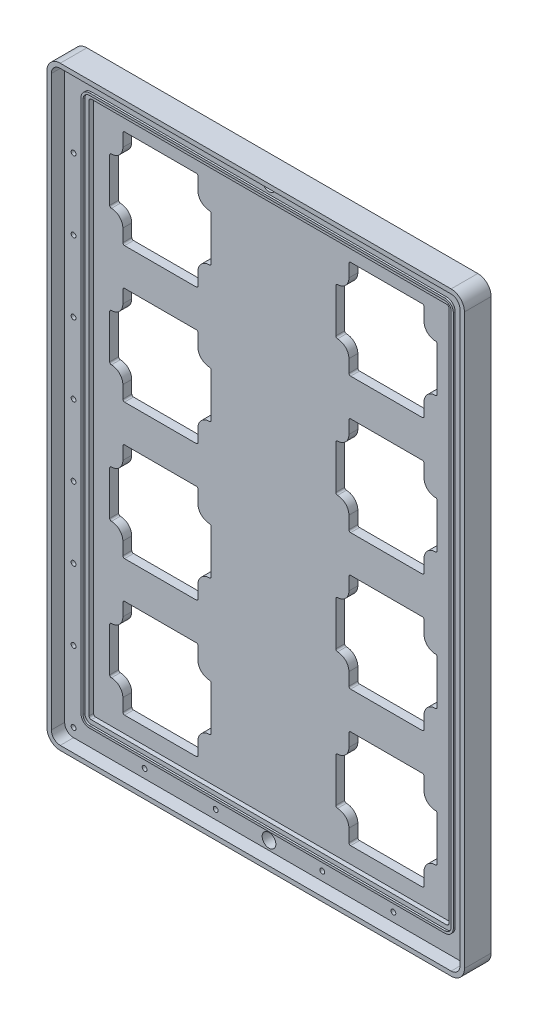
SolidWorks part; units mm, degrees
ref_plane "Front Plane" through (0, 0, 0) normal (0, 0, 1) x (1, 0, 0)
ref_plane "Top Plane" through (0, 0, 0) normal (0, 1, 0) x (1, 0, 0)
ref_plane "Right Plane" through (0, 0, 0) normal (1, 0, 0) x (0, 0, -1)
sketch "Sketch1" plane through (0, 0, 0) normal (0, 0, 1) x (1, 0, 0)
  line L1 (0, 0) -> (292.1, 0)
  line L2 (0, 0) -> (0, 419.1)
  line L3 (0, 419.1) -> (292.1, 419.1)
  line L4 (292.1, 0) -> (292.1, 419.1)
  dimension "D1" = 419.1
  dimension "D2" = 292.1
extrude "Boss-Extrude1" add sketch "Sketch1" along normal blind 9.525
sketch "Sketch4" plane through (0, 0, 9.525) normal (0, 0, 1) x (1, 0, 0)
  line L3 (0, 419.1) -> (0, 0) construction
  line L4 (6.35, 412.75) -> (285.75, 412.75) construction
  line L5 (6.35, 412.75) -> (6.35, 6.35) construction
  line L6 (6.35, 6.35) -> (285.75, 6.35) construction
  line L7 (285.75, 412.75) -> (285.75, 6.35) construction
  line L8 (292.1, 419.1) -> (0, 419.1) construction
  line L9 (292.1, 0) -> (292.1, 419.1) construction
  line L10 (0, 0) -> (292.1, 0) construction
  circle A0 centre (6.35, 6.35) radius 1.7272
  circle A1 centre (6.35, 412.75) radius 1.7272
  circle A2 centre (285.75, 412.75) radius 1.7272
  circle A3 centre (285.75, 6.35) radius 1.7272
  dimension "D5" = 3.4544
  dimension "D1" = 6.35
  dimension "D2" = 6.35
  dimension "D3" = 6.35
  dimension "D4" = 6.35
extrude "Cut-Extrude1" cut sketch "Sketch4" against normal blind 6.985
pattern_linear "LPattern2" count 8 spacing 50.8 along (0, -1, 0) of "Cut-Extrude1"
sketch "Sketch5" plane through (0, 0, 9.525) normal (0, 0, 1) x (1, 0, 0)
  line L0 (0, 419.1) -> (0, 0) construction
  line L1 (19.05, 406.4) -> (273.05, 406.4) construction
  line L2 (12.7, 400.05) -> (12.7, 19.05) construction
  line L3 (19.05, 12.7) -> (273.05, 12.7) construction
  line L4 (279.4, 400.05) -> (279.4, 19.05) construction
  line L5 (292.1, 419.1) -> (0, 419.1) construction
  line L6 (292.1, 0) -> (292.1, 419.1) construction
  line L7 (0, 0) -> (292.1, 0) construction
  line L8 (19.05, 14.732) -> (273.05, 14.732) construction
  line L9 (14.732, 400.05) -> (14.732, 19.05) construction
  line L10 (19.05, 404.368) -> (273.05, 404.368) construction
  line L11 (277.368, 400.05) -> (277.368, 19.05) construction
  line L12 (12.954, 400.05) -> (12.954, 19.05)
  line L13 (19.05, 406.146) -> (273.05, 406.146)
  line L14 (279.146, 400.05) -> (279.146, 19.05)
  line L15 (19.05, 12.954) -> (273.05, 12.954)
  line L16 (277.622, 400.05) -> (277.622, 19.05)
  line L17 (19.05, 404.622) -> (273.05, 404.622)
  line L18 (14.478, 400.05) -> (14.478, 19.05)
  line L19 (19.05, 14.478) -> (273.05, 14.478)
  arc A0 (273.05, 12.7) -> (279.4, 19.05) centre (273.05, 19.05) ccw construction
  arc A1 (12.7, 19.05) -> (19.05, 12.7) centre (19.05, 19.05) ccw construction
  arc A2 (273.05, 406.4) -> (279.4, 400.05) centre (273.05, 400.05) cw construction
  arc A3 (19.05, 406.4) -> (12.7, 400.05) centre (19.05, 400.05) ccw construction
  arc A4 (14.732, 19.05) -> (19.05, 14.732) centre (19.05, 19.05) ccw construction
  arc A5 (19.05, 404.368) -> (14.732, 400.05) centre (19.05, 400.05) ccw construction
  arc A6 (273.05, 404.368) -> (277.368, 400.05) centre (273.05, 400.05) cw construction
  arc A7 (273.05, 14.732) -> (277.368, 19.05) centre (273.05, 19.05) ccw construction
  arc A8 (19.05, 406.146) -> (12.954, 400.05) centre (19.05, 400.05) ccw
  arc A9 (273.05, 406.146) -> (279.146, 400.05) centre (273.05, 400.05) cw
  arc A10 (273.05, 12.954) -> (279.146, 19.05) centre (273.05, 19.05) ccw
  arc A11 (12.954, 19.05) -> (19.05, 12.954) centre (19.05, 19.05) ccw
  arc A12 (273.05, 404.622) -> (277.622, 400.05) centre (273.05, 400.05) cw
  arc A13 (19.05, 404.622) -> (14.478, 400.05) centre (19.05, 400.05) ccw
  arc A14 (14.478, 19.05) -> (19.05, 14.478) centre (19.05, 19.05) ccw
  arc A15 (273.05, 14.478) -> (277.622, 19.05) centre (273.05, 19.05) ccw
  dimension "D5" = 6.35
  dimension "D1" = 12.7
  dimension "D2" = 12.7
  dimension "D3" = 12.7
  dimension "D4" = 12.7
  dimension "D6" = 2.032
  dimension "D7" = 2.032
  dimension "D8" = 0.254
  dimension "D9" = 0.254
  dimension "D10" = 0.254
sketch "Sketch6" plane through (0, 0, 9.525) normal (0, 0, 1) x (1, 0, 0)
  line L0 (292.1, 419.1) -> (0, 419.1) construction
  line L1 (0, 419.1) -> (0, 0) construction
  line L24 (273.05, 401.6375) -> (19.05, 401.6375)
  line L25 (274.6375, 19.05) -> (274.6375, 400.05)
  line L26 (19.05, 17.4625) -> (273.05, 17.4625)
  line L27 (17.4625, 400.05) -> (17.4625, 19.05)
  line L28 (273.05, 401.6375) -> (19.05, 401.6375)
  line L29 (274.6375, 19.05) -> (274.6375, 400.05)
  line L30 (19.05, 17.4625) -> (273.05, 17.4625)
  line L31 (17.4625, 400.05) -> (17.4625, 19.05)
  arc A20 (19.05, 401.6375) -> (17.4625, 400.05) centre (19.05, 400.05) ccw
  arc A21 (274.6375, 400.05) -> (273.05, 401.6375) centre (273.05, 400.05) ccw
  arc A22 (273.05, 17.4625) -> (274.6375, 19.05) centre (273.05, 19.05) ccw
  arc A23 (17.4625, 19.05) -> (19.05, 17.4625) centre (19.05, 19.05) ccw
  arc A24 (19.05, 401.6375) -> (17.4625, 400.05) centre (19.05, 400.05) ccw
  arc A25 (274.6375, 400.05) -> (273.05, 401.6375) centre (273.05, 400.05) ccw
  arc A26 (273.05, 17.4625) -> (274.6375, 19.05) centre (273.05, 19.05) ccw
  arc A27 (17.4625, 19.05) -> (19.05, 17.4625) centre (19.05, 19.05) ccw
  dimension "D2" = 17.4625
  dimension "D3" = 17.4625
  dimension "D1" = 2.7305
extrude "Cut-Extrude3" cut sketch "Sketch6" against normal blind 3.175
extrude "Boss-Extrude2" add sketch "Sketch5" along normal blind 1.3335 contours L12 A11 L15 A10 L14 A9 L13 A8 A15 L19 A14 L18 A13 L17 A12 L16 region at (15.0752, 404.0248, 9.525)
fillet "Fillet1" radius 6.35 4 edges at (0, 419.1, 4.7625) (292.1, 419.1, 4.7625) (0, 0, 4.7625) (292.1, 0, 4.7625)
sketch "Sketch8" plane through (0, 0, 0) normal (0, 0, -1) x (-1, 0, 0)
  line L0 (-264.668, 370.459) -> (-264.668, 339.2678)
  line L1 (-255.27, 329.8698) -> (-255.27, 320.8782)
  line L2 (-252.4506, 318.0588) -> (-201.2442, 318.0588)
  line L3 (-198.4248, 320.8782) -> (-198.4248, 329.8698)
  line L4 (-189.0268, 339.2678) -> (-189.0268, 370.459)
  line L5 (-198.4248, 379.857) -> (-198.4248, 388.8486)
  line L6 (-201.2442, 391.668) -> (-252.4506, 391.668)
  line L7 (-255.27, 388.8486) -> (-255.27, 379.857)
  line L8 (-261.8486, 391.668) -> (-261.8486, 318.0588) construction
  line L9 (-264.668, 388.8486) -> (-189.0268, 388.8486) construction
  line L10 (-264.668, 391.668) -> (-189.0268, 391.668) construction
  line L11 (-264.668, 391.668) -> (-264.668, 318.0588) construction
  line L12 (-264.668, 318.0588) -> (-189.0268, 318.0588) construction
  line L13 (-189.0268, 391.668) -> (-189.0268, 318.0588) construction
  line L14 (-264.668, 379.857) -> (-189.0268, 379.857) construction
  line L15 (-264.668, 370.459) -> (-189.0268, 370.459) construction
  line L16 (-264.668, 339.2678) -> (-189.0268, 339.2678) construction
  line L17 (-264.668, 329.8698) -> (-189.0268, 329.8698) construction
  line L18 (-264.668, 320.8782) -> (-189.0268, 320.8782) construction
  line L19 (-255.27, 318.0588) -> (-255.27, 391.668) construction
  line L20 (-252.4506, 391.668) -> (-252.4506, 318.0588) construction
  line L21 (-201.2442, 391.668) -> (-201.2442, 318.0588) construction
  line L22 (-198.4248, 391.668) -> (-198.4248, 318.0588) construction
  line L23 (-191.8462, 318.0588) -> (-191.8462, 391.668) construction
  line L24 (-189.0268, 373.2784) -> (-264.668, 373.2784) construction
  line L27 (-201.2442, 393.7) -> (-252.4506, 393.7)
  line L28 (-257.302, 388.8486) -> (-257.302, 379.857)
  line L29 (-266.7, 370.459) -> (-266.7, 339.2678)
  line L30 (-257.302, 329.8698) -> (-257.302, 320.8782)
  line L31 (-252.4506, 316.0268) -> (-201.2442, 316.0268)
  line L32 (-196.3928, 320.8782) -> (-196.3928, 329.8698)
  line L33 (-186.9948, 339.2678) -> (-186.9948, 370.459)
  line L34 (-196.3928, 379.857) -> (-196.3928, 388.8486)
  line L35 (-285.75, 419.1) -> (-6.35, 419.1) construction
  line L36 (-292.1, 6.35) -> (-292.1, 412.75) construction
  arc A0 (-261.8486, 373.2784) -> (-255.27, 379.857) centre (-261.8486, 379.857) ccw
  arc A1 (-261.8486, 373.2784) -> (-264.668, 370.459) centre (-261.8486, 370.459) ccw
  arc A2 (-264.668, 339.2678) -> (-261.8486, 336.4484) centre (-261.8486, 339.2678) ccw
  arc A3 (-255.27, 329.8698) -> (-261.8486, 336.4484) centre (-261.8486, 329.8698) ccw
  arc A4 (-255.27, 320.8782) -> (-252.4506, 318.0588) centre (-252.4506, 320.8782) ccw
  arc A5 (-201.2442, 318.0588) -> (-198.4248, 320.8782) centre (-201.2442, 320.8782) ccw
  arc A6 (-191.8462, 336.4484) -> (-198.4248, 329.8698) centre (-191.8462, 329.8698) ccw
  arc A7 (-191.8462, 336.4484) -> (-189.0268, 339.2678) centre (-191.8462, 339.2678) ccw
  arc A8 (-189.0268, 370.459) -> (-191.8462, 373.2784) centre (-191.8462, 370.459) ccw
  arc A9 (-198.4248, 379.857) -> (-191.8462, 373.2784) centre (-191.8462, 379.857) ccw
  arc A10 (-198.4248, 388.8486) -> (-201.2442, 391.668) centre (-201.2442, 388.8486) ccw
  arc A11 (-252.4506, 391.668) -> (-255.27, 388.8486) centre (-252.4506, 388.8486) ccw
  arc A12 (-252.4506, 393.7) -> (-257.302, 388.8486) centre (-252.4506, 388.8486) ccw
  arc A13 (-261.8486, 375.3104) -> (-257.302, 379.857) centre (-261.8486, 379.857) ccw
  arc A14 (-261.8486, 375.3104) -> (-266.7, 370.459) centre (-261.8486, 370.459) ccw
  arc A15 (-266.7, 339.2678) -> (-261.8486, 334.4164) centre (-261.8486, 339.2678) ccw
  arc A16 (-257.302, 329.8698) -> (-261.8486, 334.4164) centre (-261.8486, 329.8698) ccw
  arc A17 (-257.302, 320.8782) -> (-252.4506, 316.0268) centre (-252.4506, 320.8782) ccw
  arc A18 (-201.2442, 316.0268) -> (-196.3928, 320.8782) centre (-201.2442, 320.8782) ccw
  arc A19 (-191.8462, 334.4164) -> (-196.3928, 329.8698) centre (-191.8462, 329.8698) ccw
  arc A20 (-191.8462, 334.4164) -> (-186.9948, 339.2678) centre (-191.8462, 339.2678) ccw
  arc A21 (-186.9948, 370.459) -> (-191.8462, 375.3104) centre (-191.8462, 370.459) ccw
  arc A22 (-196.3928, 379.857) -> (-191.8462, 375.3104) centre (-191.8462, 379.857) ccw
  arc A23 (-196.3928, 388.8486) -> (-201.2442, 393.7) centre (-201.2442, 388.8486) ccw
  dimension "D4" = 11.811
  dimension "D5" = 21.209
  dimension "D6" = 52.4002
  dimension "D1" = 73.6092
  dimension "D2" = 75.6412
  dimension "D3" = 2.8194
  dimension "D7" = 61.7982
  dimension "D8" = 70.7898
  dimension "D9" = 2.8194
  dimension "D10" = 9.398
  dimension "D11" = 12.2174
  dimension "D12" = 63.4238
  dimension "D13" = 66.2432
  dimension "D14" = 72.8218
  dimension "D15" = 55.2196
  dimension "D16" = 25.4
  dimension "D17" = 25.4
  dimension "D18" = 2.032
extrude "Cut-Extrude5" cut sketch "Sketch8" against normal blind 3.175
sketch "Sketch10" plane through (0, 0, 0) normal (0, 0, -1) x (-1, 0, 0)
  line L18 (-263.0805, 370.459) -> (-263.0805, 339.2678)
  line L19 (-253.6825, 329.8698) -> (-253.6825, 320.8782)
  line L20 (-252.4506, 319.6463) -> (-201.2442, 319.6463)
  line L21 (-200.0123, 320.8782) -> (-200.0123, 329.8698)
  line L22 (-190.6143, 339.2678) -> (-190.6143, 370.459)
  line L23 (-200.0123, 379.857) -> (-200.0123, 388.8486)
  line L24 (-201.2442, 390.0805) -> (-252.4506, 390.0805)
  line L25 (-253.6825, 388.8486) -> (-253.6825, 379.857)
  line L26 (-263.0805, 370.459) -> (-263.0805, 339.2678)
  line L27 (-253.6825, 329.8698) -> (-253.6825, 320.8782)
  line L28 (-252.4506, 319.6463) -> (-201.2442, 319.6463)
  line L29 (-200.0123, 320.8782) -> (-200.0123, 329.8698)
  line L30 (-190.6143, 339.2678) -> (-190.6143, 370.459)
  line L31 (-200.0123, 379.857) -> (-200.0123, 388.8486)
  line L32 (-201.2442, 390.0805) -> (-252.4506, 390.0805)
  line L33 (-253.6825, 388.8486) -> (-253.6825, 379.857)
  arc A28 (-261.8486, 371.6909) -> (-263.0805, 370.459) centre (-261.8486, 370.459) ccw
  arc A29 (-263.0805, 339.2678) -> (-261.8486, 338.0359) centre (-261.8486, 339.2678) ccw
  arc A30 (-253.6825, 329.8698) -> (-261.8486, 338.0359) centre (-261.8486, 329.8698) ccw
  arc A31 (-253.6825, 320.8782) -> (-252.4506, 319.6463) centre (-252.4506, 320.8782) ccw
  arc A32 (-201.2442, 319.6463) -> (-200.0123, 320.8782) centre (-201.2442, 320.8782) ccw
  arc A33 (-191.8462, 338.0359) -> (-200.0123, 329.8698) centre (-191.8462, 329.8698) ccw
  arc A34 (-191.8462, 338.0359) -> (-190.6143, 339.2678) centre (-191.8462, 339.2678) ccw
  arc A35 (-190.6143, 370.459) -> (-191.8462, 371.6909) centre (-191.8462, 370.459) ccw
  arc A36 (-200.0123, 379.857) -> (-191.8462, 371.6909) centre (-191.8462, 379.857) ccw
  arc A37 (-200.0123, 388.8486) -> (-201.2442, 390.0805) centre (-201.2442, 388.8486) ccw
  arc A38 (-252.4506, 390.0805) -> (-253.6825, 388.8486) centre (-252.4506, 388.8486) ccw
  arc A39 (-261.8486, 371.6909) -> (-253.6825, 379.857) centre (-261.8486, 379.857) ccw
  arc A40 (-261.8486, 371.6909) -> (-263.0805, 370.459) centre (-261.8486, 370.459) ccw
  arc A41 (-263.0805, 339.2678) -> (-261.8486, 338.0359) centre (-261.8486, 339.2678) ccw
  arc A42 (-253.6825, 329.8698) -> (-261.8486, 338.0359) centre (-261.8486, 329.8698) ccw
  arc A43 (-253.6825, 320.8782) -> (-252.4506, 319.6463) centre (-252.4506, 320.8782) ccw
  arc A44 (-201.2442, 319.6463) -> (-200.0123, 320.8782) centre (-201.2442, 320.8782) ccw
  arc A45 (-191.8462, 338.0359) -> (-200.0123, 329.8698) centre (-191.8462, 329.8698) ccw
  arc A46 (-191.8462, 338.0359) -> (-190.6143, 339.2678) centre (-191.8462, 339.2678) ccw
  arc A47 (-190.6143, 370.459) -> (-191.8462, 371.6909) centre (-191.8462, 370.459) ccw
  arc A48 (-200.0123, 379.857) -> (-191.8462, 371.6909) centre (-191.8462, 379.857) ccw
  arc A49 (-200.0123, 388.8486) -> (-201.2442, 390.0805) centre (-201.2442, 388.8486) ccw
  arc A50 (-252.4506, 390.0805) -> (-253.6825, 388.8486) centre (-252.4506, 388.8486) ccw
  arc A51 (-261.8486, 371.6909) -> (-253.6825, 379.857) centre (-261.8486, 379.857) ccw
  dimension "D1" = 1.5875
extrude "Cut-Extrude6" cut sketch "Sketch10" against normal through all
sketch "Sketch11" plane through (0, 0, 0) normal (0, 0, -1) x (-1, 0, 0)
  line L0 (-226.8474, 388.8994) -> (-226.8474, 393.7) construction
  line L1 (-261.8486, 388.8994) -> (-191.8462, 388.8994) construction
  line L2 (-261.8486, 388.8994) -> (-261.8486, 320.8274) construction
  line L3 (-261.8486, 320.8274) -> (-191.8462, 320.8274) construction
  line L4 (-191.8462, 388.8994) -> (-191.8462, 320.8274) construction
  line L5 (-201.2442, 393.7) -> (-252.4506, 393.7) construction
  line L6 (-226.8474, 320.8274) -> (-226.8474, 316.0268) construction
  line L7 (-252.4506, 316.0268) -> (-201.2442, 316.0268) construction
  line L8 (-261.8486, 354.8634) -> (-266.7, 354.8634) construction
  line L9 (-266.7, 370.459) -> (-266.7, 339.2678) construction
  line L10 (-191.8462, 354.8634) -> (-186.9948, 354.8634) construction
  line L11 (-186.9948, 339.2678) -> (-186.9948, 370.459) construction
  circle A0 centre (-261.8486, 388.8994) radius 1.1303
  circle A1 centre (-191.8462, 388.8994) radius 1.1303
  circle A2 centre (-191.8462, 320.8274) radius 1.1303
  circle A3 centre (-261.8486, 320.8274) radius 1.1303
  dimension "D3" = 2.2606
  dimension "D1" = 70.0024
  dimension "D2" = 68.072
extrude "Cut-Extrude7" cut sketch "Sketch11" against normal blind 3.9688
pattern_linear "LPattern1" count 2 spacing 161.5948 along (-1, 0, 0) count 4 spacing 96.8756 along (0, -1, 0) of "Cut-Extrude6", "Cut-Extrude5", "Cut-Extrude7"
sketch "Sketch13" plane through (0, 0, 0) normal (0, 0, -1) x (-1, 0, 0)
  line L4 (-6.35, 419.1) -> (-285.75, 419.1)
  line L5 (-292.1, 412.75) -> (-292.1, 6.35)
  line L6 (-285.75, 0) -> (-6.35, 0)
  line L7 (0, 6.35) -> (0, 412.75)
  line L8 (-285.75, -3.175) -> (-6.35, -3.175)
  line L9 (3.175, 6.35) -> (3.175, 412.75)
  line L10 (-6.35, 422.275) -> (-285.75, 422.275)
  line L11 (-295.275, 412.75) -> (-295.275, 6.35)
  line L12 (-285.75, -3.175) -> (-6.35, -3.175)
  line L13 (3.175, 6.35) -> (3.175, 412.75)
  line L14 (-6.35, 422.275) -> (-285.75, 422.275)
  line L15 (-295.275, 412.75) -> (-295.275, 6.35)
  arc A4 (-285.75, 419.1) -> (-292.1, 412.75) centre (-285.75, 412.75) ccw
  arc A5 (-292.1, 6.35) -> (-285.75, 0) centre (-285.75, 6.35) ccw
  arc A6 (-6.35, 0) -> (0, 6.35) centre (-6.35, 6.35) ccw
  arc A7 (0, 412.75) -> (-6.35, 419.1) centre (-6.35, 412.75) ccw
  arc A8 (-295.275, 6.35) -> (-285.75, -3.175) centre (-285.75, 6.35) ccw
  arc A9 (-6.35, -3.175) -> (3.175, 6.35) centre (-6.35, 6.35) ccw
  arc A10 (3.175, 412.75) -> (-6.35, 422.275) centre (-6.35, 412.75) ccw
  arc A11 (-285.75, 422.275) -> (-295.275, 412.75) centre (-285.75, 412.75) ccw
  arc A12 (-295.275, 6.35) -> (-285.75, -3.175) centre (-285.75, 6.35) ccw
  arc A13 (-6.35, -3.175) -> (3.175, 6.35) centre (-6.35, 6.35) ccw
  arc A14 (3.175, 412.75) -> (-6.35, 422.275) centre (-6.35, 412.75) ccw
  arc A15 (-285.75, 422.275) -> (-295.275, 412.75) centre (-285.75, 412.75) ccw
  dimension "D1" = 3.175
  dimension "D2" = 3.175
extrude "Boss-Extrude5" add sketch "Sketch13" against normal blind 19.05
sketch "Sketch14" plane through (0, 0, 9.525) normal (0, 0, 1) x (1, 0, 0)
  line L0 (285.75, 6.35) -> (6.35, 6.35) construction
  circle A0 centre (234.95, 6.35) radius 1.7272
  circle A1 centre (184.15, 6.35) radius 1.7272
  circle A2 centre (107.95, 6.35) radius 1.7272
  circle A3 centre (57.15, 6.35) radius 1.7272
  circle A4 centre (6.35, 6.35) radius 1.7272 construction
  dimension "D1" = 50.8
  dimension "D2" = 50.8
  dimension "D3" = 50.8
  dimension "D4" = 50.8
extrude "Cut-Extrude8" cut sketch "Sketch14" against normal blind 6.985
sketch "Sketch15" plane through (0, 0, 9.525) normal (0, 0, 1) x (1, 0, 0)
  line L0 (285.75, 6.35) -> (6.35, 6.35) construction
  circle A0 centre (146.05, 6.35) radius 4.9022
  dimension "D1" = 9.8044
extrude "Cut-Extrude9" cut sketch "Sketch15" against normal through all
pattern_linear "LPattern3" count 2 spacing 406.4 along (0, 1, 0) of "Cut-Extrude8", "Cut-Extrude9"
